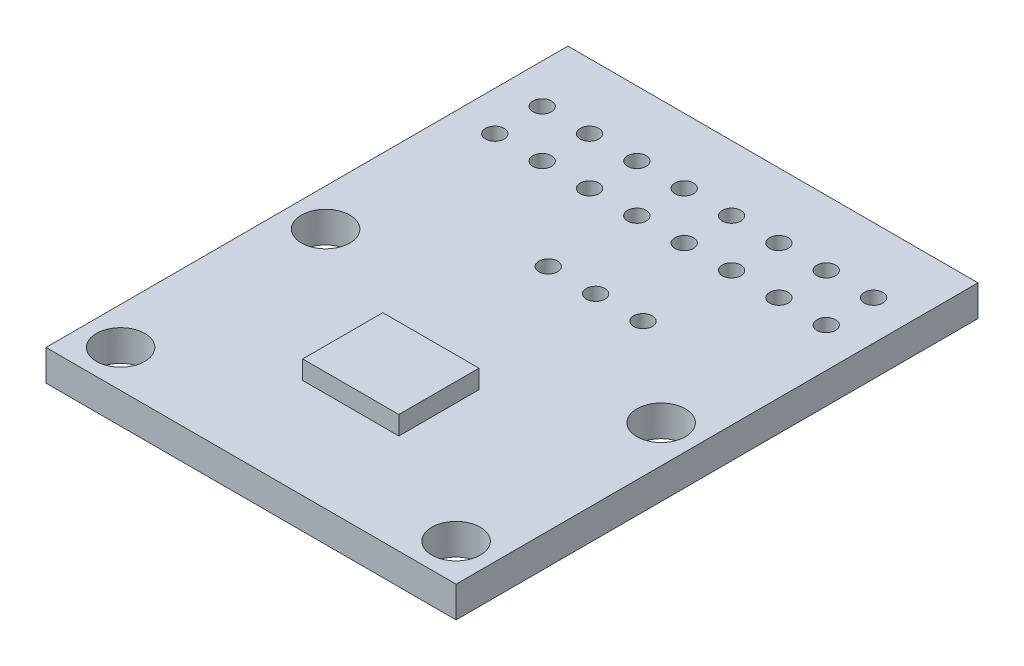
SolidWorks part; units mm, degrees
ref_plane "Front Plane" through (0, 0, 0) normal (0, 0, 1) x (1, 0, 0)
ref_plane "Top Plane" through (0, 0, 0) normal (0, 1, 0) x (1, 0, 0)
ref_plane "Right Plane" through (0, 0, 0) normal (1, 0, 0) x (0, 0, -1)
ref_plane "Plane1" through (0, 0.83, 0) normal (0, 1, 0) x (1, 0, 0)
sketch "Sketch1" plane through (0, 0.83, 0) normal (0, 1, 0) x (1, 0, 0)
  line L0 (11, -14) -> (11, 14)
  line L1 (11, 14) -> (-11, 14)
  line L2 (-11, 14) -> (-11, -14)
  line L3 (-11, -14) -> (11, -14)
extrude "Boss-Extrude1" add sketch "Sketch1" against normal blind 1.66
sketch "Sketch2" plane through (0, 0.83, 0) normal (0, 1, 0) x (-1, 0, 0)
  line L0 (-2.58, 8.65) -> (2.58, 8.65)
  line L1 (2.58, 8.65) -> (2.58, 4.35)
  line L2 (2.58, 4.35) -> (-2.58, 4.35)
  line L3 (-2.58, 4.35) -> (-2.58, 8.65)
extrude "Boss-Extrude2" add sketch "Sketch2" along normal blind 1
hole_wizard "Ø2.6 (2.6) Diameter Hole1" positions "Sketch4" profile "Sketch3" hole size "Ø2.6" standard "ANSI Metric"
sketch "Sketch4" plane through (0, -0.83, 0) normal (0, -1, 0) x (-1, 0, 0)
  point P0 (9, -1)
  point P1 (-9, -1)
  point P2 (9, -12)
  point P3 (-9, -12)
sketch "Sketch3" plane through (-9, -0.83, 1) normal (1, 0, 0) x (0, 0, -1)
  line L0 (0, 0) -> (0, 2.66)
  line L1 (0, 2.66) -> (1.3, 2.66)
  line L2 (1.3, 2.66) -> (1.3, 0)
  line L5 (1.3, 0) -> (0, 0)
  line L11 (0, -6.35) -> (0, 107.95) construction
  dimension "Thru Hole Dia." = 2.6
  dimension "Thru Hole Depth" = 2.66
ref_plane "Plane2" through (0, 0, 6.5) normal (0, 0, -1) x (-1, 0, 0)
ref_axis "Axis1" through (0, -0.963, 6.5) along (0, 1, 0)
sketch "Sketch5" plane through (0, 0.83, 0) normal (0, 1, 0) x (1, 0, 0)
  line L0 (34.6032, 177.1459) -> (301.2699, 177.1459) construction
  line L2 (-2.58, 4.7678) -> (5.0833, 4.7678)
  line L3 (-2.58, 4.7678) -> (-2.58, 1.6977)
  line L4 (11, -14) -> (11, 14)
  line L5 (11, 14) -> (-11, 14)
  line L6 (-11, 14) -> (-11, -14)
  line L7 (-11, -14) -> (11, -14)
  line L8 (11, -14) -> (11, 14)
  line L9 (11, 14) -> (-11, 14)
  line L10 (-11, 14) -> (-11, -14)
  line L11 (-11, -14) -> (11, -14)
  line L12 (-2.58, -8.65) -> (2.58, -8.65)
  line L13 (-2.58, -4.35) -> (-2.58, -8.65)
  line L14 (2.58, -4.35) -> (-2.58, -4.35)
  line L15 (2.58, -8.65) -> (2.58, -4.35)
  line L16 (-2.58, -8.65) -> (2.58, -8.65)
  line L17 (-2.58, -4.35) -> (-2.58, -8.65)
  line L18 (2.58, -4.35) -> (-2.58, -4.35)
  line L19 (2.58, -8.65) -> (2.58, -4.35)
  line L20 (-2.58, 1.6977) -> (5.0833, 1.6977)
  line L21 (5.0833, 4.7678) -> (5.0833, 1.6977)
  line L22 (-10.0162, 12.2512) -> (10.0162, 12.2512)
  line L23 (-10.0162, 12.2512) -> (-10.0162, 6.2261)
  line L24 (-10.0162, 6.2261) -> (10.0162, 6.2261)
  line L25 (10.0162, 12.2512) -> (10.0162, 6.2261)
  point P18 (0, 12.2512)
  dimension "D1" = 0
  dimension "D2" = 0
sketch "Sketch6" plane through (0, 0.83, 0) normal (0, 1, 0) x (1, 0, 0)
  line L0 (-8.89, 10.5086) -> (-8.89, 7.9686) construction
  line L1 (8.89, 10.5086) -> (8.89, 7.9686) construction
  line L2 (-8.89, 9.2386) -> (8.89, 9.2386) construction
  line L3 (0, 12.2512) -> (0, 6.2261) construction
  line L4 (-2.58, -8.65) -> (2.58, -8.65)
  line L5 (2.58, -8.65) -> (2.58, -4.35)
  line L6 (2.58, -4.35) -> (-2.58, -4.35)
  line L7 (-2.58, -4.35) -> (-2.58, -8.65)
  line L8 (-2.58, -8.65) -> (2.58, -8.65) construction
  line L9 (2.58, -8.65) -> (2.58, -4.35) construction
  line L10 (2.58, -4.35) -> (-2.58, -4.35) construction
  line L11 (-2.58, -4.35) -> (-2.58, -8.65) construction
  line L12 (11, -14) -> (11, 14)
  line L13 (11, 14) -> (-11, 14)
  line L14 (-11, 14) -> (-11, -14)
  line L15 (-11, -14) -> (11, -14)
  line L16 (11, -14) -> (11, 14) construction
  line L17 (11, 14) -> (-11, 14) construction
  line L18 (-11, 14) -> (-11, -14) construction
  line L19 (-11, -14) -> (11, -14) construction
  line L20 (5.0833, 4.7678) -> (-2.58, 4.7678)
  line L21 (5.0833, 1.6977) -> (5.0833, 4.7678)
  line L22 (-2.58, 1.6977) -> (5.0833, 1.6977)
  line L23 (-2.58, 4.7678) -> (-2.58, 1.6977)
  line L24 (5.0833, 4.7678) -> (-2.58, 4.7678) construction
  line L25 (5.0833, 1.6977) -> (5.0833, 4.7678) construction
  line L26 (-2.58, 1.6977) -> (5.0833, 1.6977) construction
  line L27 (-2.58, 4.7678) -> (-2.58, 1.6977) construction
  line L28 (10.0162, 12.2512) -> (-10.0162, 12.2512)
  line L29 (-10.0162, 12.2512) -> (-10.0162, 6.2261)
  line L30 (-10.0162, 6.2261) -> (10.0162, 6.2261)
  line L31 (10.0162, 6.2261) -> (10.0162, 12.2512)
  line L32 (10.0162, 12.2512) -> (-10.0162, 12.2512) construction
  line L33 (-10.0162, 12.2512) -> (-10.0162, 6.2261) construction
  line L34 (-10.0162, 6.2261) -> (10.0162, 6.2261) construction
  line L35 (10.0162, 6.2261) -> (10.0162, 12.2512) construction
  circle A0 centre (-8.89, 10.5086) radius 0.5
  circle A1 centre (-8.89, 7.9686) radius 0.5
  circle A2 centre (-6.35, 10.5086) radius 0.5
  circle A3 centre (-6.35, 7.9686) radius 0.5
  circle A4 centre (-3.81, 10.5086) radius 0.5
  circle A5 centre (-3.81, 7.9686) radius 0.5
  circle A6 centre (-1.27, 10.5086) radius 0.5
  circle A7 centre (-1.27, 7.9686) radius 0.5
  circle A8 centre (1.27, 10.5086) radius 0.5
  circle A9 centre (1.27, 7.9686) radius 0.5
  circle A10 centre (3.81, 10.5086) radius 0.5
  circle A11 centre (3.81, 7.9686) radius 0.5
  circle A12 centre (6.35, 10.5086) radius 0.5
  circle A13 centre (6.35, 7.9686) radius 0.5
  circle A14 centre (8.89, 10.5086) radius 0.5
  circle A15 centre (8.89, 7.9686) radius 0.5
  circle A16 centre (-1.2884, 3.2327) radius 0.5
  circle A17 centre (1.2516, 3.2327) radius 0.5
  circle A18 centre (3.7916, 3.2327) radius 0.5
  point P52 (0, 9.2386)
  point P53 (0, 9.2386)
  point P65 (1.2516, 4.7678)
  point P67 (5.0833, 3.2327)
  dimension "D5" = 1
  dimension "D6" = 2.54
  dimension "D1" = 0
  dimension "D2" = 0
  dimension "D3" = 0
  dimension "D4" = 0
  dimension "D7" = 8
  dimension "D8" = 3
extrude "Cut-Extrude1" cut sketch "Sketch6" against normal through all
